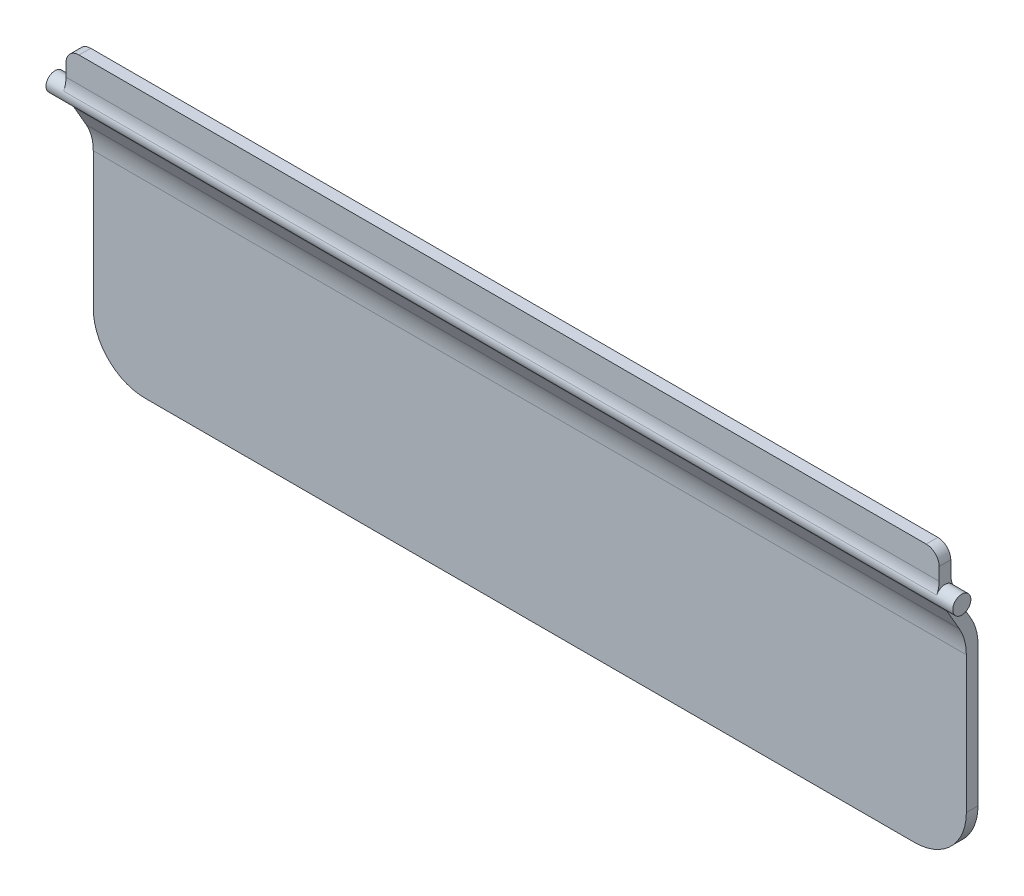
SolidWorks part; units mm, degrees
material "PVC Rigid"
ref_plane "Front Plane" through (0, 0, 0) normal (0, 0, 1) x (1, 0, 0)
ref_plane "Top Plane" through (0, 0, 0) normal (0, 1, 0) x (1, 0, 0)
ref_plane "Right Plane" through (0, 0, 0) normal (1, 0, 0) x (0, 0, -1)
sketch "Sketch1" plane through (0, 0, 0) normal (1, 0, 0) x (0, 0, -1)
  line L0 (-7.5, 73.75) -> (-7.5, 22.5442)
  line L1 (-7.5, -73.75) -> (7.5, -73.75) construction
  line L2 (-7.5, -73.75) -> (-7.5, 73.75) construction
  line L3 (-7.5, 73.75) -> (7.5, 73.75) construction
  line L4 (7.5, -73.75) -> (7.5, 73.75) construction
  line L5 (0, 73.75) -> (0, -73.75) construction
  line L6 (-7.5, 0) -> (7.5, 0) construction
  line L7 (-7.5, 22.5442) -> (3, 4.3577)
  line L8 (3, 4.3577) -> (3, -73.75)
  line L9 (3, -73.75) -> (7.5, -73.75)
  line L10 (7.5, -73.75) -> (7.5, 5.5635)
  line L11 (7.5, 5.5635) -> (-3, 23.75)
  line L12 (-3, 23.75) -> (-3, 73.75)
  line L13 (-3, 73.75) -> (-7.5, 73.75)
  point P0 (0, 0)
  dimension "D1" = 147.5
  dimension "D2" = 15
  dimension "D3" = 4.5
  dimension "D4" = 4.5
  dimension "D6" = 50
  dimension "D7" = 150
extrude "Boss-Extrude1" add sketch "Sketch1" along normal mid plane 337
sketch "Sketch2" plane through (0, 0, 0) normal (1, 0, 0) x (0, 0, -1)
  line L0 (-7.5, 22.5442) -> (-3, 23.75) construction
  circle A0 centre (-5.25, 23.1471) radius 3.5
  dimension "D1" = 7
extrude "Boss-Extrude2" add sketch "Sketch2" along normal mid plane 350
fillet "Fillet1" radius 20 6 edges at (0, 4.3577, -3) (0, 5.5635, -7.5) (168.5, -73.75, -5.25) (-168.5, -73.75, -5.25) (-168.5, 73.75, 5.25) (168.5, 73.75, 5.25)
sketch "Sketch3" plane through (0, 0, 3) normal (0, 0, -1) x (-1, 0, 0)
  line L0 (-168.5, 25.8281) -> (-168.5, 53.75) construction
  line L1 (-168.5, 38.75) -> (168.5, 38.75)
  line L2 (-168.5, 38.75) -> (-168.5, 73.75)
  line L3 (-168.5, 73.75) -> (168.5, 73.75)
  line L4 (168.5, 38.75) -> (168.5, 73.75)
  line L5 (-168.5, 38.75) -> (168.5, 73.75) construction
  line L6 (-168.5, 73.75) -> (168.5, 38.75) construction
  line L7 (168.5, 25.8281) -> (168.5, 53.75) construction
  line L8 (-148.5, 73.75) -> (148.5, 73.75) construction
  point P4 (0, 56.25)
  dimension "D1" = 35
extrude "Cut-Extrude1" cut sketch "Sketch3" against normal through all
fillet "Fillet2" radius 10 4 edges at (0, 25.8281, 7.5) (0, 19.7003, 5.8581) (0, 21.9503, 1.961) (0, 25.8281, 3)
fillet "Fillet3" radius 5 2 edges at (-168.5, 38.75, 5.25) (168.5, 38.75, 5.25)
